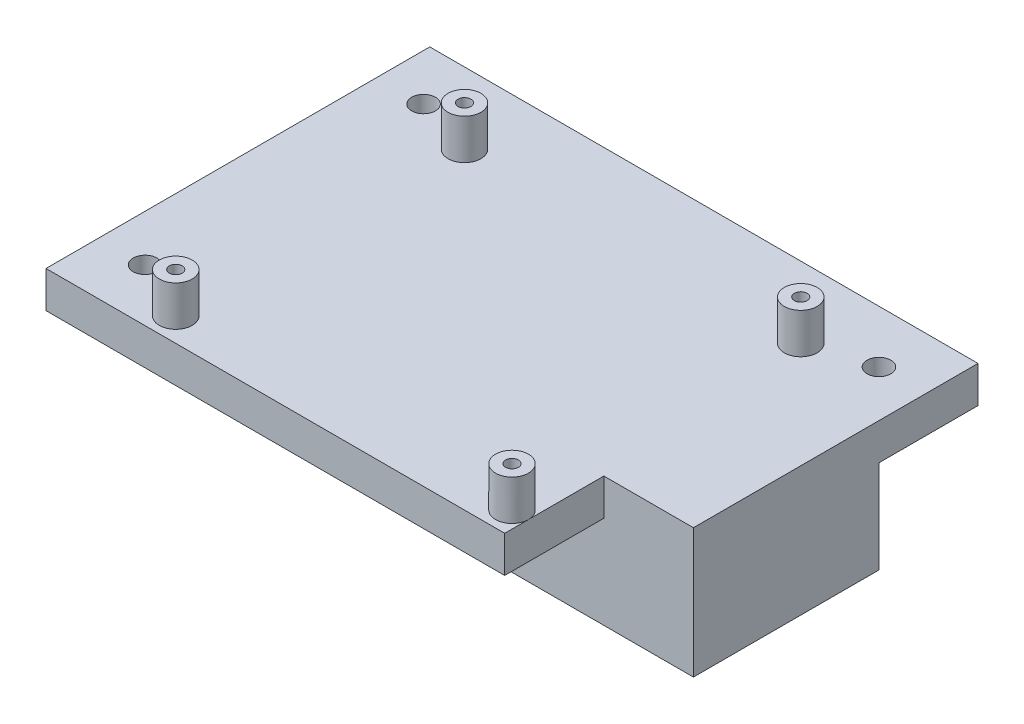
SolidWorks part; units mm, degrees
material "PETG"
ref_plane "Front Plane" through (0, 0, 0) normal (0, 0, 1) x (1, 0, 0)
ref_plane "Top Plane" through (0, 0, 0) normal (0, 1, 0) x (1, 0, 0)
ref_plane "Right Plane" through (0, 0, 0) normal (1, 0, 0) x (0, 0, -1)
sketch "Sketch1" plane through (0, 0, 0) normal (0, 1, 0) x (1, 0, 0)
  line L0 (-62.3, 38.1) -> (-75, 38.1) construction
  line L1 (-75, -25.3625) -> (75, -25.3625)
  line L2 (-75, -25.3625) -> (-75, 25.3625)
  line L3 (-75, 25.3625) -> (75, 25.3625)
  line L4 (75, -25.3625) -> (75, 25.3625)
  line L5 (-75, 52.5) -> (75, 52.5)
  line L6 (-75, 52.5) -> (-75, -52.5)
  line L7 (-75, -52.5) -> (75, -52.5)
  line L8 (75, 52.5) -> (75, -52.5)
  line L11 (62.3, 38.1) -> (75, 38.1) construction
  circle A0 centre (-62.3, 38.1) radius 3.25
  circle A1 centre (62.3, 38.1) radius 3.25
  circle A2 centre (-62.3, -38.1) radius 3.25
  circle A3 centre (62.3, -38.1) radius 3.25
  point P4 (-75, 0)
  point P5 (0, 25.3625)
  dimension "D4" = 6.5
  dimension "D1" = 50.725
  dimension "D2" = 150
  dimension "D3" = 105
  dimension "D5" = 38.1
  dimension "D6" = 12.7
  dimension "D7" = 38.1
extrude "Boss-Extrude1" add sketch "Sketch1" along normal blind 10 contours L1 L4 L3 L2 | L8 L1 L6 L7 | L8 L5 L6 L3 region at (0, 0, 0) region at (0, 0, 38.945) region at (0, 0, -38.945)
extrude "Boss-Extrude2" add sketch "Sketch1<3>" against normal blind 25.4 contours L1 L4 L3 L2 region at (0, 0, 0)
sketch "Sketch1<3>" plane through (0, 0, 0) normal (0, 1, 0) x (1, 0, 0) same geometry as "Sketch1"
sketch "Sketch2" plane through (0, 10, 0) normal (0, 1, 0) x (1, 0, 0)
  line L0 (-46, 33) -> (-46, -46) construction
  line L1 (-46, -46) -> (46, -46) construction
  line L2 (46, -46) -> (46, 33) construction
  line L3 (46, 33) -> (-46, 33) construction
  line L4 (-75, -52.5) -> (75, -52.5) construction
  line L6 (-75, 52.5) -> (75, 52.5) construction
  line L8 (-46, 0) -> (46, 0) construction
  circle A0 centre (-46, 33) radius 4.5
  circle A1 centre (-46, 33) radius 1.75
  circle A2 centre (46, 33) radius 4.5
  circle A3 centre (46, 33) radius 1.75
  circle A4 centre (46, -46) radius 4.5
  circle A5 centre (46, -46) radius 1.75
  circle A6 centre (-46, -46) radius 4.5
  circle A7 centre (-46, -46) radius 1.75
  point P19 (0, 0)
  dimension "D1" = 3.5
  dimension "D2" = 9
  dimension "D3" = 6.5
  dimension "D4" = 92
  dimension "D5" = 19.5
extrude "Boss-Extrude3" add sketch "Sketch2" along normal blind 11
extrude "Cut-Extrude4" cut sketch "Sketch2<3>" against normal up to next contours A1 | A3 | A5 | A7 region at (-46, 10, -33)
sketch "Sketch2<3>" plane through (0, 10, 0) normal (0, 1, 0) x (1, 0, 0) same geometry as "Sketch2"
sketch "Sketch3" plane through (0, 10, 0) normal (0, 1, 0) x (1, 0, 0)
  circle A0 centre (-46, 33) radius 3.2
  circle A1 centre (46, 33) radius 3.2
  circle A2 centre (46, -46) radius 3.2
  circle A3 centre (-46, -46) radius 3.2
  dimension "D1" = 6.4
extrude "Cut-Extrude3" cut sketch "Sketch3" against normal up to next from offset 3.5 offset against normal yes
sketch "Sketch4" plane through (0, 10, 0) normal (0, 1, 0) x (1, 0, 0)
  line L0 (-75, -25.3625) -> (75, -25.3625) construction
  line L1 (75, -52.5) -> (50.5, -52.5)
  line L2 (75, -52.5) -> (75, -25.3625)
  line L3 (75, -25.3625) -> (50.5, -25.3625)
  line L4 (50.5, -52.5) -> (50.5, -25.3625)
  circle A0 centre (46, -46) radius 4.5 construction
extrude "Cut-Extrude5" cut sketch "Sketch4" against normal up to vertex (10 mm away) up to point (75, 0, 25.3625)
equation "\"tol_dia_id_intfc\"= 0.0500mm ' For hole diameters - Interference fit"
equation "\"tol_dia_id_slip\"= 0.0750mm ' For hole diameters - Slip fit"
equation "\"tol_dia_id_clear\"= 0.1000mm ' For hole diameters - Clearance fit"
equation "\"tol_dia_od_intfc\"= 0.0500mm ' For shaft diameters - Interference fit"
equation "\"tol_dia_od_slip\"= 0.0750mm ' For shaft diameters - Slip fit"
equation "\"tol_dia_od_clear\"= 0.1000mm ' For shaft diameters - Clearance fit"
equation "\"tol_general_intfc\"= 0.0250mm ' For general parts (Horiz) - Interference fit"
equation "\"tol_general_slip\"= 0.0375mm ' For general parts (Horiz) - Slip fit"
equation "\"tol_general_clear\"= 0.0500mm ' For general parts (Horiz) - Clearance fit"
equation "\"tol_layer_intfc\"= 0.0250mm ' For all parts (Vert) - Interference fit"
equation "\"tol_layer_slip\"= 0.0375mm ' For all parts (Vert) - Slip fit"
equation "\"tol_layer_clear\"= 0.0500mm ' For all parts (Vert) - Clearance fit"
equation "\"tol_corner_rad\"= 0.100mm ' For corners that fit into other parts"
equation "\"D1@Sketch1\"=50.80mm-\"tol_general_slip\"*2"
